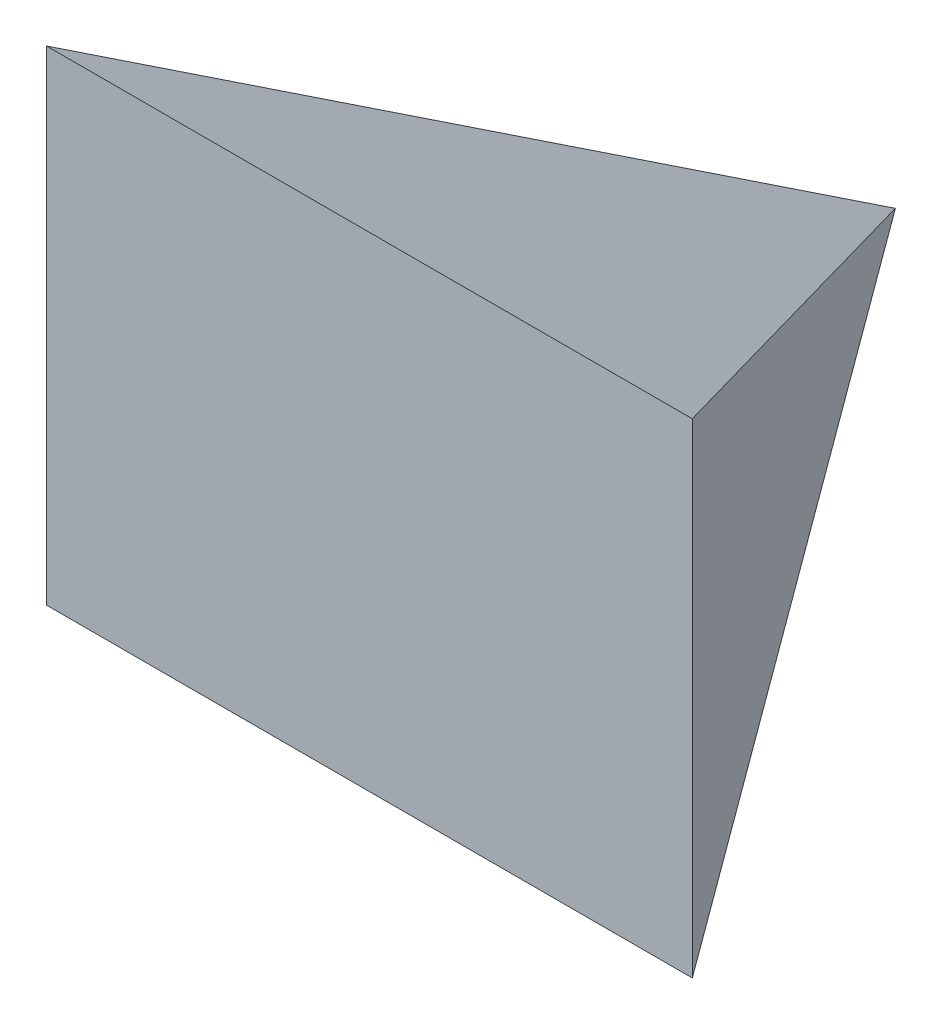
SolidWorks part; units mm, degrees
ref_plane "Plan de face" through (0, 0, 0) normal (0, 0, 1) x (1, 0, 0)
ref_plane "Plan de dessus" through (0, 0, 0) normal (0, 1, 0) x (1, 0, 0)
ref_plane "Plan de droite" through (0, 0, 0) normal (1, 0, 0) x (0, 0, -1)
sketch "Esquisse4" plane through (0, 0, 0) normal (0, 0, 1) x (1, 0, 0)
  line L1 (0, 87.3927) -> (400, 87.3927)
  line L2 (0, 87.3927) -> (0, 387.3927)
  line L3 (0, 387.3927) -> (400, 387.3927)
  line L4 (400, 87.3927) -> (400, 387.3927)
  dimension "D1" = 400
  dimension "D2" = 300
ref_plane "Plan1" through (185.9485, 247.9313, 0) normal (-0.6, -0.8, 0) x (-0.8, 0.6, 0)
ref_plane "Plan2" through (-41.9485, 55.9313, 0) normal (-0.6, 0.8, 0) x (0.8, 0.6, 0)
ref_axis "Axe1" through (200, 237.3927, -525) along (0, 0, 1)
sketch "Esquisse5" plane through (185.9485, 247.9313, 0) normal (-0.6, -0.8, 0) x (-0.8, 0.6, 0)
  line L0 (-267.5644, 0) -> (-17.5644, 325.8063)
  line L1 (-17.5644, 525) -> (-17.5644, -25) construction
  line L2 (-17.5644, 325.8063) -> (232.4356, 0)
  dimension "D1" = 75
  dimension "D2" = 325.8063
extrude "Boss.-Extru.1" add sketch "Esquisse4" against normal blind 325.81
sketch "Esquisse9" plane through (0, 387.3927, 0) normal (0, 1, 0) x (1, 0, 0)
  line L0 (0, 0) -> (200, 325.81)
  line L1 (200, 325.81) -> (400, 0)
  line L2 (400, 0) -> (400, 335.81)
  line L3 (400, 335.81) -> (0, 335.81)
  line L4 (0, 335.81) -> (0, 0)
  line L5 (400, 325.81) -> (0, 325.81) construction
  dimension "D1" = 10
extrude "Enlèv. mat.-Extru.1" cut sketch "Esquisse9" against normal through all
sketch "Esquisse10" plane through (0, 0, 0) normal (-0.8522, 0, -0.5232) x (-0.5232, 0, 0.8522)
  line L0 (0, 387.3927) -> (-382.2985, 237.3927)
  line L1 (-382.2985, 237.3927) -> (0, 87.3927)
  line L2 (0, 87.3927) -> (-392.2985, 87.3927)
  line L3 (-392.2985, 87.3927) -> (-392.2985, 387.3927)
  line L4 (-392.2985, 387.3927) -> (0, 387.3927)
  line L6 (-382.2985, 87.3927) -> (-382.2985, 387.3927) construction
  dimension "D1" = 10
extrude "Enlèv. mat.-Extru.3" cut sketch "Esquisse10" along direction (-1, 0, 0) on the side against the normal through all
